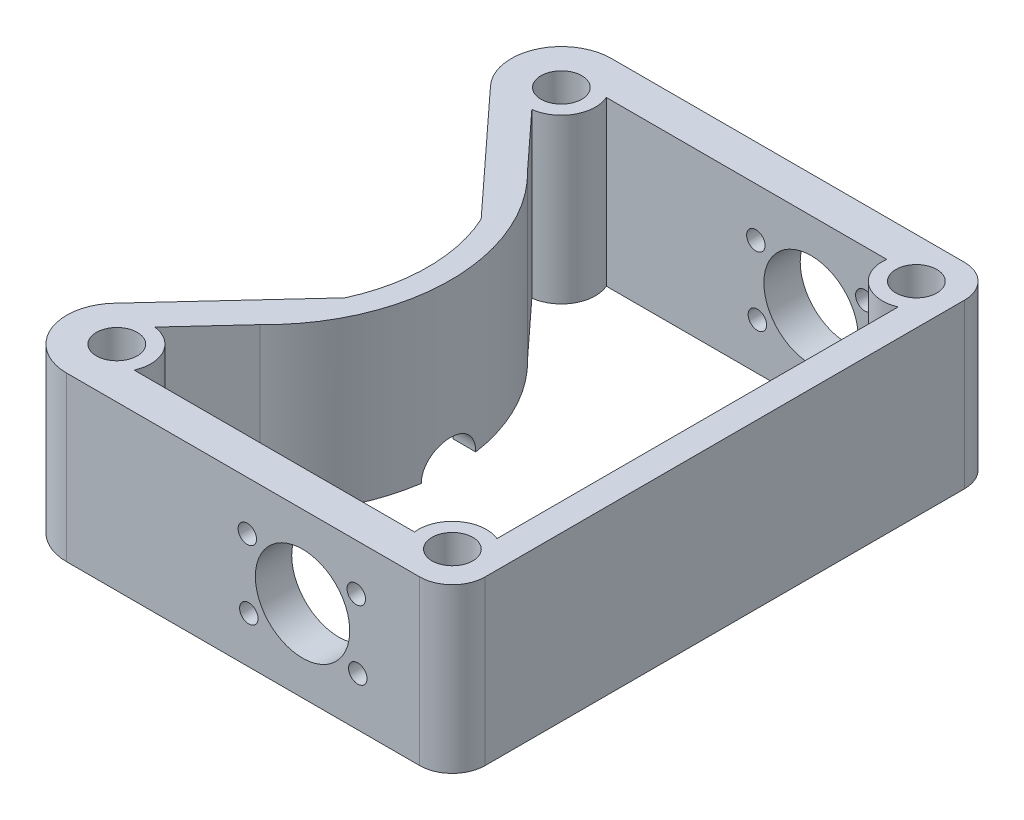
SolidWorks part; units mm, degrees
material "TPU"
ref_plane "Front Plane" through (0, 0, 0) normal (0, 0, 1) x (1, 0, 0)
ref_plane "Top Plane" through (0, 0, 0) normal (0, 1, 0) x (1, 0, 0)
ref_plane "Right Plane" through (0, 0, 0) normal (1, 0, 0) x (0, 0, -1)
sketch "Sketch1" plane through (0, 0, 0) normal (0, 1, 0) x (1, 0, 0)
  line L0 (66.675, 17.145) -> (66.675, 128.905) construction
  line L1 (-28.575, 9.525) -> (66.675, 9.525)
  line L2 (-28.575, 9.525) -> (-28.575, 17.9917)
  line L3 (-28.575, 17.9917) -> (66.675, 17.9917)
  line L4 (66.675, 9.525) -> (66.675, 17.9917)
  line L5 (-28.575, 9.525) -> (66.675, 17.9917) construction
  line L6 (-28.575, 17.9917) -> (66.675, 9.525) construction
  line L9 (-28.575, 9.525) -> (59.055, 9.525) construction
  point P0 (19.05, 13.7583)
  point P5 (0, 0)
  point P15 (19.05, 9.525)
  dimension "D1" = 95.25
  dimension "D2" = 8.4667
extrude "Boss-Extrude1" add sketch "Sketch1" along normal blind 38.1
sketch "Sketch2" plane through (0, 38.1, 0) normal (0, 1, 0) x (1, 0, 0)
  line L1 (60.325, 9.525) -> (66.675, 9.525)
  line L2 (60.325, 9.525) -> (60.325, 136.525)
  line L3 (60.325, 136.525) -> (66.675, 136.525)
  line L4 (66.675, 9.525) -> (66.675, 136.525)
  line L6 (32.8756, 15.875) -> (32.8756, 130.175) construction
  line L7 (-20.4, 15.875) -> (58.5, 15.875) construction
  line L8 (58.5, 130.175) -> (-20.4, 130.175) construction
  dimension "D1" = 127
  dimension "D2" = 6.35
extrude "Boss-Extrude2" add sketch "Sketch2" against normal up to surface (38.1 mm away) up to face at (19.05, 0, -13.7583)
sketch "Sketch3" plane through (0, 38.1, 0) normal (0, 1, 0) x (1, 0, 0)
  line L0 (-28.575, 17.9917) -> (-28.575, 9.525) construction
  line L1 (60.325, 136.525) -> (-28.575, 136.525)
  line L2 (60.325, 136.525) -> (60.325, 128.0583)
  line L3 (60.325, 128.0583) -> (-28.575, 128.0583)
  line L4 (-28.575, 136.525) -> (-28.575, 128.0583)
extrude "Boss-Extrude3" add sketch "Sketch3" against normal up to surface (38.1 mm away) up to face at (32.8083, 0, -54.6806)
sketch "Sketch4" plane through (0, 0, -136.525) normal (0, 0, -1) x (-1, 0, 0)
  line L0 (3.175, 38.1) -> (-66.675, 38.1) construction
  line L1 (-66.675, 19.05) -> (3.175, 19.05) construction
  line L2 (-66.675, 0) -> (-66.675, 38.1) construction
  line L5 (28.575, 19.05) -> (3.175, 19.05) construction
  line L6 (28.575, 0) -> (28.575, 38.1) construction
  circle A0 centre (-31.75, 19.05) radius 11
  point P7 (-31.75, 38.1)
  dimension "D1" = 22
  dimension "D2" = 25.4
extrude "Cut-Extrude1" cut sketch "Sketch4" against normal through all contours A0 region at (31.75, 19.05, -136.525)
sketch "Sketch5" plane through (0, 0, -136.525) normal (0, 0, -1) x (-1, 0, 0)
  circle A0 centre (-18.8777, 26.7049) radius 2.1527
  circle A1 centre (-19.2285, 10.8337) radius 2.1527
  circle A2 centre (-44.6223, 11.3951) radius 2.1527
  circle A3 centre (-44.2715, 27.2663) radius 2.1526
  circle A4 centre (-44.6223, 11.3951) radius 2.1527 construction
  circle A5 centre (-18.8777, 26.7049) radius 2.1526 construction
  circle A6 centre (-19.2285, 10.8337) radius 2.1527 construction
  circle A9 centre (-44.2715, 27.2663) radius 2.1526 construction
extrude "Cut-Extrude2" cut sketch "Sketch5" against normal through all
fillet "Fillet1" radius 7.62 2 edges at (66.675, 19.05, -9.525) (66.675, 19.05, -136.525)
sketch "Sketch10" plane through (0, 38.1, 0) normal (0, 1, 0) x (1, 0, 0)
  line L0 (-28.575, 9.525) -> (59.055, 9.525) construction
  line L2 (-28.575, 17.9917) -> (-28.575, 9.525)
  line L5 (66.675, 73.025) -> (-147.9374, 73.025) construction
  line L7 (-28.575, 136.525) -> (-34.925, 136.525)
  line L11 (-34.925, 25.781) -> (-5.996, 57.15)
  line L15 (-28.575, 17.9917) -> (-28.575, 22.225)
  line L16 (-28.575, 22.225) -> (-10.4944, 41.8306)
  line L17 (-28.575, 123.825) -> (-10.4944, 104.2194)
  line L18 (-34.925, 120.269) -> (-5.996, 88.9)
  line L19 (-10.4944, 41.8306) -> (-5.996, 57.15) construction
  line L22 (-28.575, 136.525) -> (-28.575, 123.825)
  line L26 (-34.925, 136.525) -> (-34.925, 120.269)
  line L27 (-34.925, 25.781) -> (-34.925, 9.525)
  line L28 (-34.925, 9.525) -> (-28.575, 9.525)
  line L29 (66.675, 17.145) -> (66.675, 128.905) construction
  arc A0 (-5.996, 57.15) -> (-5.996, 88.9) centre (-40.6312, 73.025) ccw
  arc A2 (-10.4944, 104.2194) -> (-10.4944, 41.8306) centre (-40.6312, 73.025) cw
  point P3 (0, 0)
  point P10 (0, 0)
  point P13 (-11.0673, 73.025)
  point P14 (0, 0)
  point P25 (0, 0)
  dimension "D7" = 31.75
  dimension "D6" = 38.1
  dimension "D1" = 16.256
  dimension "D2" = 6.35
  dimension "D3" = 12.7
  dimension "D4" = 42.672
  dimension "D5" = 26.67
extrude "Boss-Extrude4" add sketch "Sketch10" against normal up to surface (38.1 mm away) up to face at (26.0966, 0, -73.025)
sketch "Sketch12" plane through (60.325, 0, 0) normal (-1, 0, 0) x (0, 0, 1)
  line L0 (-88.9, 0) -> (-79.375, 0) construction
  line L1 (-88.9, 0) -> (-57.15, 0) construction
  line L2 (-57.15, 0) -> (-66.675, 0) construction
  line L3 (-79.375, 0) -> (-66.675, 0)
  arc A0 (-79.375, 0) -> (-66.675, 0) centre (-73.025, 0) cw
  point P9 (0, 0)
  dimension "D1" = 12.7
extrude "Cut-Extrude8" cut sketch "Sketch12" along normal up to surface (95.25 mm away) up to face at (-34.925, 19.05, -128.397)
fillet "Fillet2" 2 edges at (-34.925, 19.05, -120.269) (-34.925, 19.05, -136.525) type full round first side face at (-20.4605, 19.05, -104.5845) second side face at (42.1188, 27.2663, -136.525) middle face at (-34.925, 19.05, -128.397)
sketch "Sketch13" plane through (0, 0, 0) normal (0, -1, 0) x (-1, 0, 0)
  line L0 (-82.55, 73.025) -> (49917.45, 73.025) construction
  line L1 (-66.675, 17.145) -> (-66.675, 128.905) construction
  point P4 (-66.675, 73.025)
fillet "Fillet3" 2 edges at (-34.925, 19.05, -25.781) (-34.925, 19.05, -9.525) type full round first side face at (-20.4605, 19.05, -41.4655) second side face at (42.1188, 27.2663, -9.525) middle face at (-34.925, 19.05, -17.653)
fillet "Fillet4" radius 6.35 2 edges at (60.325, 19.05, -128.0583) (60.325, 19.05, -17.9917)
sketch "Sketch15" plane through (0, 38.1, 0) normal (0, 1, 0) x (1, 0, 0)
  line L0 (-2.5312, 73.025) -> (66.675, 73.025) construction
  line L1 (66.675, 17.145) -> (66.675, 128.905) construction
  circle A0 centre (-23.2361, 124.8361) radius 4.7625
  circle A1 centre (-23.2361, 124.8361) radius 7.9375
  arc A3 (-23.2361, 136.525) -> (-31.8288, 116.9117) centre (-23.2361, 124.8361) ccw construction
  arc A4 (-5.996, 57.15) -> (-5.996, 88.9) centre (-40.6312, 73.025) ccw construction
  circle A5 centre (-23.2361, 21.2139) radius 7.9375
  circle A6 centre (-23.2361, 21.2139) radius 4.7625
  dimension "D1" = 9.525
  dimension "D2" = 3.175
extrude "Boss-Extrude5" add sketch "Sketch15" against normal up to surface (38.1 mm away) up to face at (9.1156, 0, -73.025)
sketch "Sketch16" plane through (0, 0, 0) normal (0, -1, 0) x (-1, 0, 0)
  line L0 (-2.7429, 73.025) -> (-66.675, 73.025) construction
  line L1 (-66.675, 17.145) -> (-66.675, 128.905) construction
  circle A0 centre (23.2361, 124.8361) radius 4.7625
  arc A1 (-2.2756, 79.375) -> (-2.2756, 66.675) centre (40.6312, 73.025) ccw construction
  circle A2 centre (23.2361, 21.2139) radius 4.7625
  dimension "D1" = 9.525
extrude "Cut-Extrude9" cut sketch "Sketch16" against normal through all
sketch "Sketch17" plane through (0, 38.1, 0) normal (0, 1, 0) x (1, 0, 0)
  line L0 (59.055, 9.525) -> (66.675, 17.145) construction
  line L1 (62.865, 13.335) -> (44.9045, 31.2955) construction
  line L2 (59.055, 9.525) -> (50.0747, 18.5053) construction
  line L3 (50.0747, 18.5053) -> (53.8847, 22.3153) construction
  line L4 (53.8847, 22.3153) -> (57.6947, 26.1253) construction
  line L5 (57.6947, 26.1253) -> (66.675, 17.145) construction
  line L6 (66.675, 73.025) -> (2.7429, 73.025) construction
  line L7 (66.675, 17.145) -> (66.675, 128.905) construction
  line L8 (57.6947, 119.9247) -> (66.675, 128.905) construction
  line L9 (53.8847, 123.7347) -> (57.6947, 119.9247) construction
  line L10 (50.0747, 127.5447) -> (53.8847, 123.7347) construction
  line L11 (59.055, 136.525) -> (50.0747, 127.5447) construction
  line L12 (62.865, 132.715) -> (44.9045, 114.7545) construction
  line L13 (59.055, 136.525) -> (66.675, 128.905) construction
  circle A0 centre (57.2523, 18.9477) radius 4.7625
  circle A1 centre (57.2523, 18.9477) radius 7.9375
  arc A3 (-10.4944, 41.8306) -> (-10.4944, 104.2194) centre (-40.6312, 73.025) ccw construction
  circle A4 centre (57.2523, 127.1023) radius 7.9375
  circle A5 centre (57.2523, 127.1023) radius 4.7625
  dimension "D1" = 9.525
  dimension "D2" = 3.175
  dimension "D3" = 25.4
  dimension "D4" = 12.7
extrude "Boss-Extrude6" add sketch "Sketch17" against normal up to surface (38.1 mm away) up to face at (-23.2361, 0, -129.5986)
sketch "Sketch18" plane through (0, 0, 0) normal (0, -1, 0) x (-1, 0, 0)
  line L0 (-66.675, 73.025) -> (-2.7429, 73.025) construction
  line L1 (-66.675, 17.145) -> (-66.675, 128.905) construction
  circle A0 centre (-57.2523, 127.1023) radius 4.7625
  arc A1 (-2.2756, 79.375) -> (-2.2756, 66.675) centre (40.6312, 73.025) ccw construction
  circle A2 centre (-57.2523, 18.9477) radius 4.7625
  dimension "D1" = 9.525
extrude "Cut-Extrude10" cut sketch "Sketch18" against normal through all
